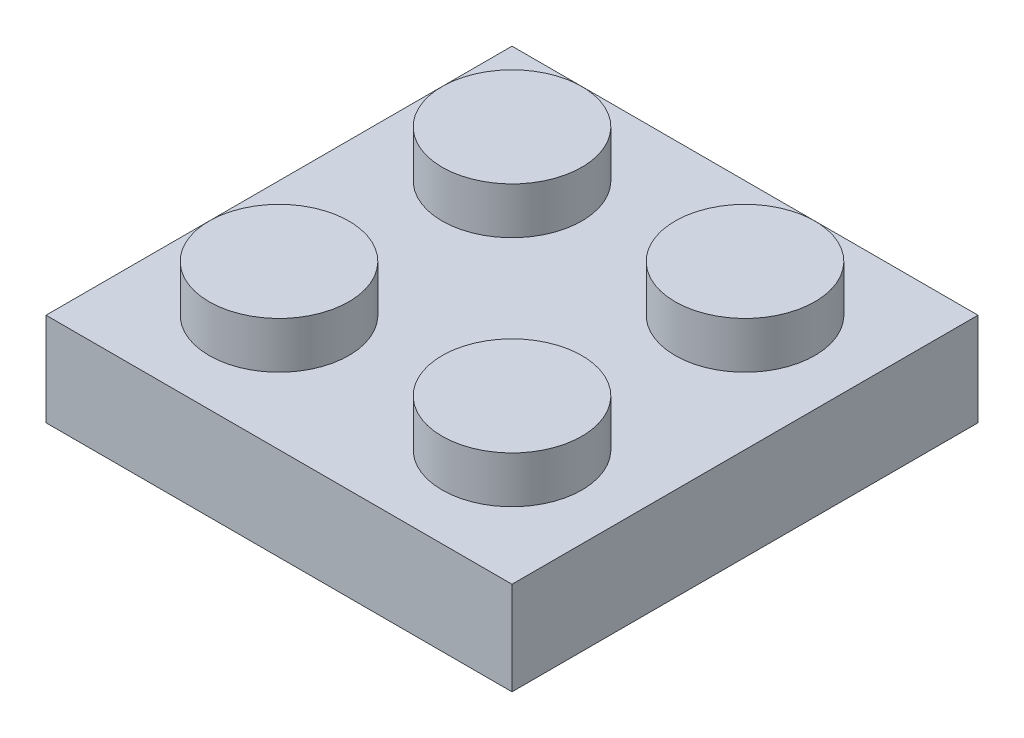
SolidWorks part; units mm, degrees
ref_plane "Front Plane" through (0, 0, 0) normal (0, 0, 1) x (1, 0, 0)
ref_plane "Top Plane" through (0, 0, 0) normal (0, 1, 0) x (1, 0, 0)
ref_plane "Right Plane" through (0, 0, 0) normal (1, 0, 0) x (0, 0, -1)
sketch "Sketch1" plane through (0, 0, 0) normal (0, 1, 0) x (1, 0, 0)
  line L0 (5, 10) -> (5, 0)
  line L1 (0, 0) -> (10, 0)
  line L2 (0, 0) -> (0, 10)
  line L3 (0, 10) -> (10, 10)
  line L4 (10, 0) -> (10, 10)
  line L5 (1, 9) -> (9, 9)
  line L6 (1, 9) -> (1, 1)
  line L7 (1, 1) -> (9, 1)
  line L8 (9, 9) -> (9, 1)
  line L10 (10, 10) -> (7.5, 10)
  line L11 (10, 10) -> (10, 7.5)
  line L12 (10, 7.5) -> (7.5, 7.5)
  line L13 (7.5, 10) -> (7.5, 7.5)
  circle A0 centre (5, 5) radius 2.0355
  circle A1 centre (7.5, 7.5) radius 1.5
  circle A2 centre (5, 5) radius 1.5
  point P9 (5, 9)
  point P10 (5, 10)
  point P11 (1, 5)
  point P12 (0, 5)
  dimension "D4" = 3
  dimension "D1" = 10
  dimension "D2" = 8
  dimension "D3" = 2.5
extrude "Boss-Extrude1" add sketch "Sketch1" along normal blind 1 contours L7 L6 L5 L0 L3 L2 L1 | A0 L0 L5 L6 L7 | A2 L0 A0 | L0 A2 | L0 A2 | A2 L0 A0 | A1 L5 L0 A0 | L13 L3 L0 L5 | L3 L13 L5 L8 L12 L4 | A1 L8 L5 | L13 A1 L12 | L12 A1 L13 | A1 A0 L0 L7 L8 | L4 L12 L8 L7 L0 L1 region at (6.25, 0, -9.5) region at (4.8882, 0, -9.5) region at (5.6784, 0, -8.0747) region at (2.7099, 0, -5) region at (9.0312, 0, -9.0312) region at (5.7615, 0, -6.8385) region at (4.9545, 0, -6.7678) region at (8.1366, 0, -8.1366) region at (8.6649, 0, -8.6649) region at (7.2878, 0, -7.2878) region at (5.6366, 0, -5) region at (4.3634, 0, -5) region at (7.4229, 0, -3.2124) region at (9.5, 0, -7.4099)
extrude "Boss-Extrude3" add sketch "Sketch1<4>" against normal blind 1 contours A2 L0 A0 | A2 L0 A0 | L7 L6 L5 L0 L3 L2 L1 | L4 L12 L8 L7 L0 L1 | L3 L13 L5 L8 L12 L4 | L13 L3 L0 L5 region at (6.25, 0, -9.5) region at (4.8882, 0, -9.5) region at (9.0312, 0, -9.0312) region at (5.7615, 0, -6.8385) region at (4.9545, 0, -6.7678) region at (9.5, 0, -7.4099)
sketch "Sketch1<4>" plane through (0, 0, 0) normal (0, 1, 0) x (1, 0, 0) same geometry as "Sketch1"
sketch "Sketch2" plane through (0, 1, 0) normal (0, 1, 0) x (1, 0, 0)
  line L0 (0, 0) -> (10, 0) construction
  line L1 (10, 0) -> (10, 10) construction
  circle A0 centre (7.5, 2.5) radius 1.5
  circle A1 centre (2.5, 2.5) radius 1.5
  circle A2 centre (2.5, 7.5) radius 1.5
  circle A3 centre (7.5, 7.5) radius 1.5
  dimension "D1" = 3
  dimension "D2" = 2.5
  dimension "D3" = 2.5
  dimension "D4" = 2
  dimension "D5" = 2
extrude "Boss-Extrude4" add sketch "Sketch2" along normal blind 1
